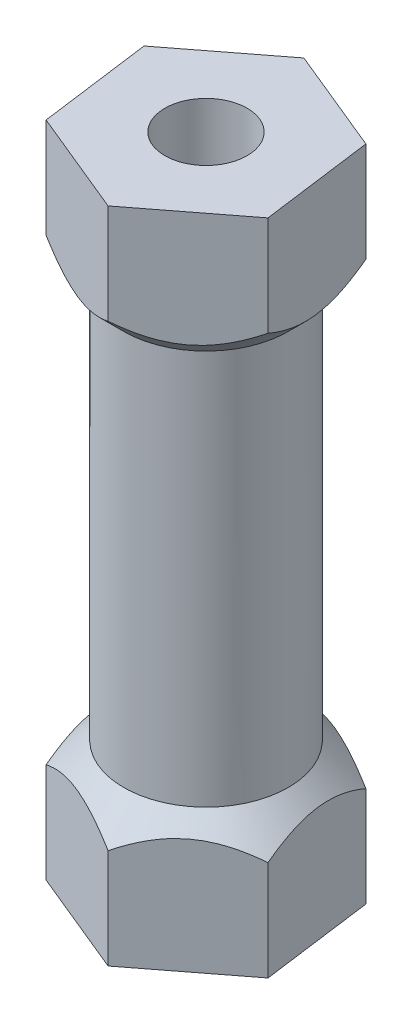
SolidWorks part; units mm, degrees
material "7050-T73510"
ref_plane "前视基准面" through (0, 0, 0) normal (0, 0, 1) x (1, 0, 0)
ref_plane "上视基准面" through (0, 0, 0) normal (0, 1, 0) x (1, 0, 0)
ref_plane "右视基准面" through (0, 0, 0) normal (1, 0, 0) x (0, 0, -1)
sketch "草图1" plane through (0, 0, 0) normal (0, 1, 0) x (1, 0, 0)
  circle A0 centre (0, 0) radius 2.5
  dimension "D1" = 5
extrude "凸台-拉伸1" add sketch "草图1" along normal blind 20
sketch "草图2" plane through (0, 20, 0) normal (0, 1, 0) x (1, 0, 0)
  line L1 (3.2029, -1.3196) -> (2.7443, 2.114)
  line L2 (2.7443, 2.114) -> (-0.4586, 3.4336)
  line L3 (-0.4586, 3.4336) -> (-3.2029, 1.3196)
  line L4 (-3.2029, 1.3196) -> (-2.7443, -2.114)
  line L5 (-2.7443, -2.114) -> (0.4586, -3.4336)
  line L6 (0.4586, -3.4336) -> (3.2029, -1.3196)
  circle A0 centre (0, 0) radius 3 construction
  dimension "D1" = 6
extrude "凸台-拉伸2" add sketch "草图2" against normal blind 3
sketch "草图3" plane through (0, 0, 0) normal (0, -1, 0) x (1, 0, 0)
  line L6 (3.2029, 1.3196) -> (0.4586, 3.4336)
  line L7 (0.4586, 3.4336) -> (-2.7443, 2.114)
  line L8 (-2.7443, 2.114) -> (-3.2029, -1.3196)
  line L9 (-3.2029, -1.3196) -> (-0.4586, -3.4336)
  line L10 (-0.4586, -3.4336) -> (2.7443, -2.114)
  line L11 (2.7443, -2.114) -> (3.2029, 1.3196)
  line L12 (3.2029, 1.3196) -> (0.4586, 3.4336)
  line L13 (0.4586, 3.4336) -> (-2.7443, 2.114)
  line L14 (-2.7443, 2.114) -> (-3.2029, -1.3196)
  line L15 (-3.2029, -1.3196) -> (-0.4586, -3.4336)
  line L16 (-0.4586, -3.4336) -> (2.7443, -2.114)
  line L17 (2.7443, -2.114) -> (3.2029, 1.3196)
  dimension "D1" = 0
extrude "凸台-拉伸3" add sketch "草图3" against normal blind 3
chamfer "倒角1" distance 1 angle 45 2 edges at (0, 3, -2.5) (0, 17, 2.5)
sketch "草图4" plane through (0, 0, 0) normal (0, 1, 0) x (-1, 0, 0)
  circle A0 centre (0, 0) radius 1.25
  dimension "D1" = 2.5
extrude "切除-拉伸1" cut sketch "草图4" along normal blind 8
cosmetic thread "装饰螺纹线2"
sketch "草图5" plane through (0, 20, 0) normal (0, -1, 0) x (-1, 0, 0)
  circle A0 centre (0, 0) radius 1.25
  dimension "D1" = 2.5
extrude "切除-拉伸2" cut sketch "草图5" along normal blind 8
cosmetic thread "装饰螺纹线1"
